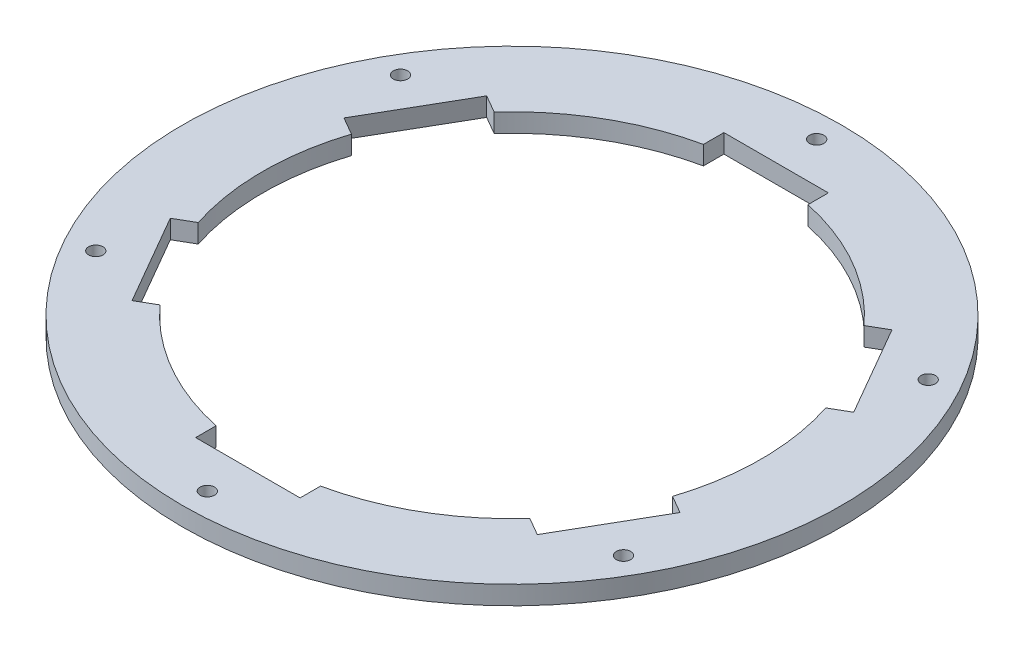
SolidWorks part; units mm, degrees
material "6061 Alloy"
ref_plane "Front Plane" through (0, 0, 0) normal (0, 0, 1) x (1, 0, 0)
ref_plane "Top Plane" through (0, 0, 0) normal (0, 1, 0) x (1, 0, 0)
ref_plane "Right Plane" through (0, 0, 0) normal (1, 0, 0) x (0, 0, -1)
sketch "Sketch1" plane through (0, 0, 0) normal (0, 1, 0) x (1, 0, 0)
  line L0 (-13.335, -62.2139) -> (-13.335, -66.1054)
  line L1 (13.335, -62.2139) -> (13.335, -66.1054)
  line L2 (-13.335, -67.437) -> (13.335, -67.437)
  line L3 (13.335, -66.1054) -> (13.335, -67.437)
  line L4 (-13.335, -66.1054) -> (-13.335, -67.437)
  circle A0 centre (0, 0) radius 63.627
  circle A1 centre (0, 0) radius 84.1375
  circle A2 centre (0, 0) radius 67.437
  circle A3 centre (0, -77.7875) radius 1.8288
  dimension "D1" = 127.254
  dimension "D2" = 168.275
  dimension "D8" = 3.6576
  dimension "D4" = 13.335
  dimension "D5" = 13.335
  dimension "D7" = 77.7875
  dimension "D3" = 3.81
extrude "Boss-Extrude1" add sketch "Sketch1" along normal blind 4.7625 contours L1 A2 L0 A0 | A1 A2 A0 region at (-15.233, 0, 64.1597) region at (-81.7577, 0, 0)
pattern_circular "CirPattern1" count 6 over 360 about axis through (0, 4.7625, 0) along (0, 1, 0) of face at (-13.335, 2.3813, 64.8255) of face at (13.335, 2.3813, 64.8255) of face at (0, 4.7625, 79.6163) of face at (0, 2.3813, 67.437)
sketch "Sketch2" plane through (0, 0, 0) normal (1, 0, 0) x (0, 0, -1)
  line L0 (84.1375, 4.7625) -> (-84.1375, 4.7625) construction
  line L1 (-84.1375, 0) -> (84.1375, 0) construction
  line L2 (84.1375, 4.7625) -> (-84.1375, 4.7625)
  line L3 (-84.1375, 0) -> (84.1375, 0)
  line L4 (0, 0) -> (0, 4.7625) construction
  circle A0 centre (-83.2231, 0) radius 2.667
  dimension "D1" = 5.334
  dimension "D2" = 0.9144
revolve "Cut-Revolve1" [suppressed] cut sketch "Sketch2" angle 360 about L4
sketch "Sketch4" plane through (0, 0, 0) normal (0, -1, 0) x (1, 0, 0)
  line L0 (0, 0) -> (35.4013, -61.3168) construction
  line L1 (0, 0) -> (0, -39.7137) construction
  circle A0 centre (35.4013, -61.3168) radius 5.588
  dimension "D2" = 11.176
  dimension "D1" = 70.8025
  dimension "D3" = 30
extrude "Cut-Extrude1" cut sketch "Sketch4" against normal blind 1.905 contours A0 region at (35.4013, 0, -61.3168)
pattern_circular "CirPattern2" count 3 over 360 about axis through (0, 0, 0) along (0, 1, 0) of "Cut-Extrude1"
equation "\"Middle Coupler Inner Daimeter\"= 4.5in"
equation "\"Middle Coupler  Wall Thickness\" = 0.25in"
equation "\"Middle Coupler Bottom Thickness\"= 0.2in"
equation "\"Bearing Rail Offset\"= 0.45in"
equation "\"3-56 UNF Tap\"= 0.089in"
equation "\"3-56 UNF Clearance\"= 0.104in"
equation "\"Ball Bearing Distance\"= 0.03in"
equation "\"D1@Sketch1\"=\"Middle Coupler Inner Daimeter\"+0.5+0.005*2in"
equation "\"TCA Outer Diameter\" = 6.625in"
equation "\"D2@Sketch1\"=\"TCA Outer Diameter\""
equation "\"D4@Sketch1\"=0.50 + (0.05/2)"
equation "\"D5@Sketch1\"=\"D4@Sketch1\""
equation "\"D7@Sketch1\"=(\"D2@Sketch1\"-0.5)/2"
equation "\"D8@Sketch1\"=\"6-32 Clearance\""
equation "\"D2@Sketch2\"=\"Interstage Aeroframe Wall Thickness\"/2"
equation "\"Interstage Aeroframe Wall Thickness\" = 0.072in"
equation "\"D1@Sketch4\"=((\"Middle Coupler Inner Daimeter\"+0.625in)/2in+0.225in)"
equation "\"Compression Spring OD\"= 0.42in"
equation "\"10-24 Tap\"= 0.157in"
equation "\"10-24 Clearance\"= 0.196in"
equation "\"D2@Sketch4\"=\"Compression Spring OD\"+0.02"
equation "\"D3@Sketch1\"=0.125in+(0.05/2)"
equation "\"Lower Stage Fuselage Wall Thickness\" = 0.25in"
equation "\"6-32 Tap\" = 0.107in"
equation "\"1/4-20 Tap\" = 0.201in"
equation "\"3-48 Tap\"= 0.079in"
equation "\"12-24 Tap\" = 0.177in"
equation "\"3-48 Clearance\" = 0.104in"
equation "\"6-32 Clearance\" = 0.144"
